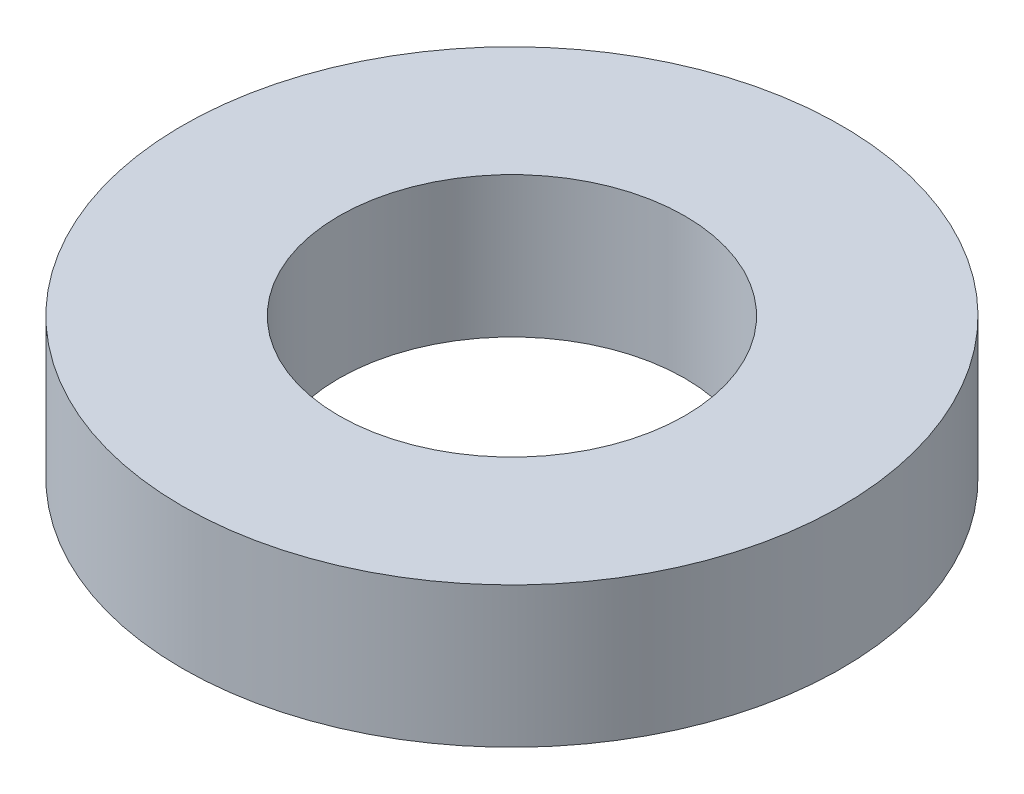
SolidWorks part; units mm, degrees
ref_plane "Front Plane" through (0, 0, 0) normal (0, 0, 1) x (1, 0, 0)
ref_plane "Top Plane" through (0, 0, 0) normal (0, 1, 0) x (1, 0, 0)
ref_plane "Right Plane" through (0, 0, 0) normal (1, 0, 0) x (0, 0, -1)
sketch "Sketch1" plane through (0, 0, 0) normal (0, 1, 0) x (1, 0, 0)
  circle A0 centre (0, 0) radius 2.5
  circle A1 centre (0, 0) radius 4.7625
  dimension "D1" = 5
  dimension "D2" = 9.525
extrude "Boss-Extrude1" add sketch "Sketch1" along normal blind 2.032
